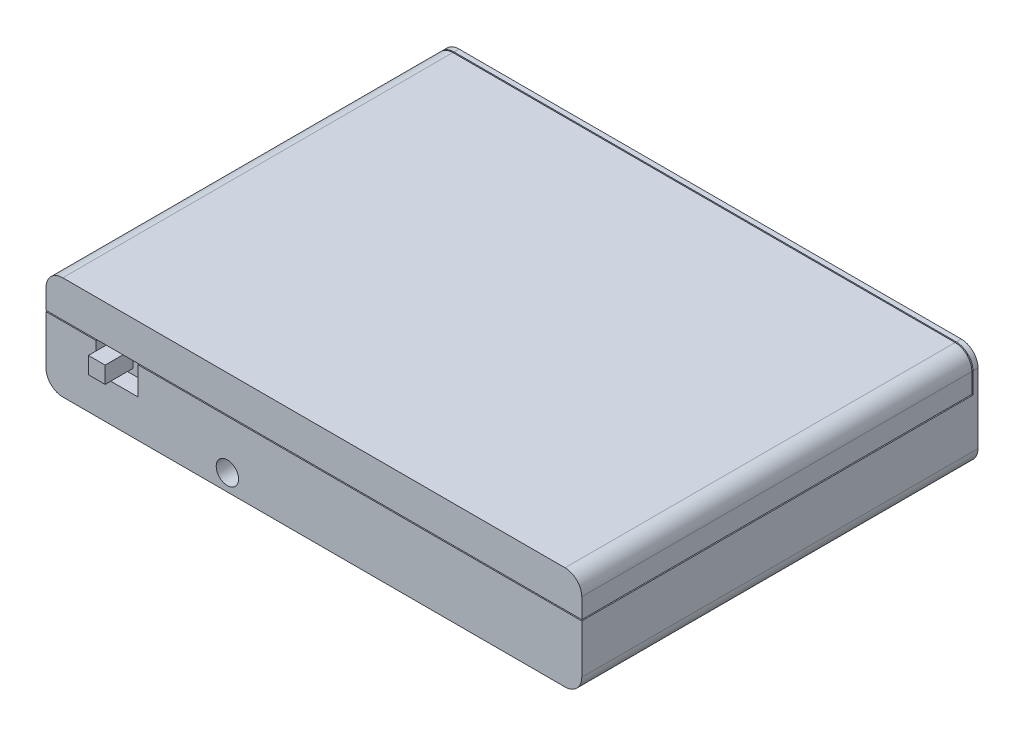
SolidWorks part; units mm, degrees
ref_plane "Front Plane" through (0, 0, 0) normal (0, 0, 1) x (1, 0, 0)
ref_plane "Top Plane" through (0, 0, 0) normal (0, 1, 0) x (1, 0, 0)
ref_plane "Right Plane" through (0, 0, 0) normal (1, 0, 0) x (0, 0, -1)
sketch "Sketch1" plane through (0, 0, 0) normal (0, 1, 0) x (1, 0, 0)
  line L1 (-48, 35.5) -> (48, 35.5)
  line L2 (-48, 35.5) -> (-48, -35.5)
  line L3 (-48, -35.5) -> (48, -35.5)
  line L4 (48, 35.5) -> (48, -35.5)
  line L5 (-48, 35.5) -> (48, -35.5) construction
  line L6 (-48, -35.5) -> (48, 35.5) construction
  point P0 (0, 0)
  dimension "D1" = 71
  dimension "D2" = 96
extrude "Box" add sketch "Sketch1" along normal blind 9.25 and the other way blind 9.25
sketch "Sketch2" plane through (0, 0, 35.5) normal (0, 0, 1) x (1, 0, 0)
  line L0 (-39, 0) -> (-48, 0) construction
  line L1 (-39, 2.5) -> (-31.5, 2.5)
  line L2 (-39, 2.5) -> (-39, -2.5)
  line L3 (-39, -2.5) -> (-31.5, -2.5)
  line L4 (-31.5, 2.5) -> (-31.5, -2.5)
  line L5 (-39, 2.5) -> (-31.5, -2.5) construction
  line L6 (-39, -2.5) -> (-31.5, 2.5) construction
  line L7 (-48, -9.25) -> (-48, 9.25) construction
  point P0 (-35.25, 0)
  point P9 (0, 0)
  dimension "D1" = 7.5
  dimension "D2" = 5
  dimension "D3" = 9
extrude "Switch Hole" cut sketch "Sketch2" against normal blind 3
sketch "Sketch4" plane through (0, 0, 32.5) normal (0, 0, 1) x (1, 0, 0)
  line L0 (-36.9046, 0) -> (-31.5, 0) construction
  line L1 (-38.4046, -1.5) -> (-35.4046, -1.5)
  line L2 (-38.4046, -1.5) -> (-38.4046, 1.5)
  line L3 (-38.4046, 1.5) -> (-35.4046, 1.5)
  line L4 (-35.4046, -1.5) -> (-35.4046, 1.5)
  line L5 (-38.4046, -1.5) -> (-35.4046, 1.5) construction
  line L6 (-38.4046, 1.5) -> (-35.4046, -1.5) construction
  line L7 (-31.5, -2.5) -> (-31.5, 2.5) construction
  point P0 (-36.9046, 0)
  dimension "D1" = 3
  dimension "D2" = 3
extrude "Switch" add sketch "Sketch4" along normal blind 5
sketch "Sketch5" plane through (0, 0, 35.5) normal (0, 0, 1) x (1, 0, 0)
  line L0 (-48, -6.25) -> (-15.5, -6.25) construction
  line L1 (-48, -9.25) -> (-48, 9.25) construction
  line L2 (-15.5, -6.25) -> (-15.5, -9.25) construction
  line L3 (-48, -9.25) -> (48, -9.25) construction
  circle A0 centre (-15.5, -6.25) radius 2
  dimension "D1" = 32.5
  dimension "D2" = 3
extrude "Wire Hole" cut sketch "Sketch5" against normal blind 5
ref_plane "Plane1" through (0, 0, -34.5) normal (0, 0, -1) x (-1, 0, 0)
sketch "Sketch7" plane through (0, 0, 35.5) normal (0, 0, 1) x (1, 0, 0)
  line L0 (-48, -9.25) -> (-48, 9.25) construction
  line L1 (-48, 2.5) -> (48, 2.5)
  line L2 (-48, 2.5) -> (-48, 2.7)
  line L3 (-48, 2.7) -> (48, 2.7)
  line L4 (48, 2.5) -> (48, 2.7)
  line L5 (48, -9.25) -> (48, 9.25) construction
  line L6 (-31.5, 2.5) -> (-39, 2.5) construction
  point P10 (-48, 2.7019)
  dimension "D1" = 0.2
extrude "Lid Indicator Front" cut sketch "Sketch7" against normal blind 1
sketch "Sketch8" plane through (-48, 0, 0) normal (-1, 0, 0) x (0, 0, 1)
  line L0 (-34.5, 10.175) -> (-34.5, -10.175) construction
  line L1 (35.5, 2.7) -> (-34.5, 2.7)
  line L2 (35.5, 2.7) -> (35.5, 2.5)
  line L3 (35.5, 2.5) -> (-34.5, 2.5)
  line L4 (-34.5, 2.7) -> (-34.5, 2.5)
  point P5 (0, 0)
extrude "Lid Indicator Left" cut sketch "Sketch8" against normal blind 1
sketch "Sketch9" plane through (48, 0, 0) normal (1, 0, 0) x (0, 0, -1)
  line L0 (34.5, -10.175) -> (34.5, 10.175) construction
  line L1 (-35.5, 2.7) -> (34.5, 2.7)
  line L2 (-35.5, 2.7) -> (-35.5, 2.5)
  line L3 (-35.5, 2.5) -> (34.5, 2.5)
  line L4 (34.5, 2.7) -> (34.5, 2.5)
  point P5 (0, 0)
extrude "Lid Indicator Right" cut sketch "Sketch9" against normal blind 1
sketch "Sketch10" plane through (0, 9.25, 0) normal (0, 1, 0) x (1, 0, 0)
  line L0 (10.175, 34.5) -> (-10.175, 34.5) construction
  line L1 (48, 34.4) -> (-48, 34.4)
  line L2 (48, 34.4) -> (48, 34.6)
  line L3 (48, 34.6) -> (-48, 34.6)
  line L4 (-48, 34.4) -> (-48, 34.6)
  line L5 (48, 34.4) -> (-48, 34.6) construction
  line L6 (48, 34.6) -> (-48, 34.4) construction
  line L7 (-48, 35.5) -> (-48, -35.5) construction
  line L8 (48, -35.5) -> (48, 35.5) construction
  point P0 (0, 34.5)
  point P11 (0, 0)
  dimension "D1" = 0.1
extrude "Lid Indicator Top" cut sketch "Sketch10" against normal blind 1
sketch "Sketch11" plane through (-48, 0, 0) normal (-1, 0, 0) x (0, 0, 1)
  line L0 (-34.5, 2.5) -> (34.5, 2.5) construction
  line L1 (-34.4, 8.25) -> (-34.6, 8.25)
  line L2 (-34.4, 8.25) -> (-34.4, 2.5)
  line L3 (-34.4, 2.5) -> (-34.6, 2.5)
  line L4 (-34.6, 8.25) -> (-34.6, 2.5)
  line L5 (-34.6, 2.6) -> (-34.4, 2.6) construction
  line L6 (-34.5, 2.7) -> (-34.5, 2.5) construction
  point P12 (-34.5, 2.6)
  point P13 (-34.5, 2.6)
extrude "Lid Indicator Left Snippet" cut sketch "Sketch11" against normal blind 1
sketch "Sketch12" plane through (48, 0, 0) normal (1, 0, 0) x (0, 0, -1)
  line L0 (34.4, 2.6) -> (34.6, 2.6) construction
  line L1 (34.4, 8.25) -> (34.6, 8.25)
  line L2 (34.4, 8.25) -> (34.4, 2.5)
  line L3 (34.4, 2.5) -> (34.6, 2.5)
  line L4 (34.6, 8.25) -> (34.6, 2.5)
  line L5 (34.5, 2.5) -> (34.5, 2.7) construction
  line L6 (-34.5, 2.5) -> (34.5, 2.5) construction
  point P7 (34.5, 2.6)
  point P10 (34.5, 2.6)
extrude "Lid Indicator Right Snippet" cut sketch "Sketch12" against normal blind 1
fillet "Bottom ROund" radius 3 2 edges at (48, -9.25, 0) (-48, -9.25, 0)
fillet "Top Round" radius 3 4 edges at (-48, 9.25, 0.55) (48, 9.25, 0.55) (-48, 9.25, -35.05) (48, 9.25, -35.05)
